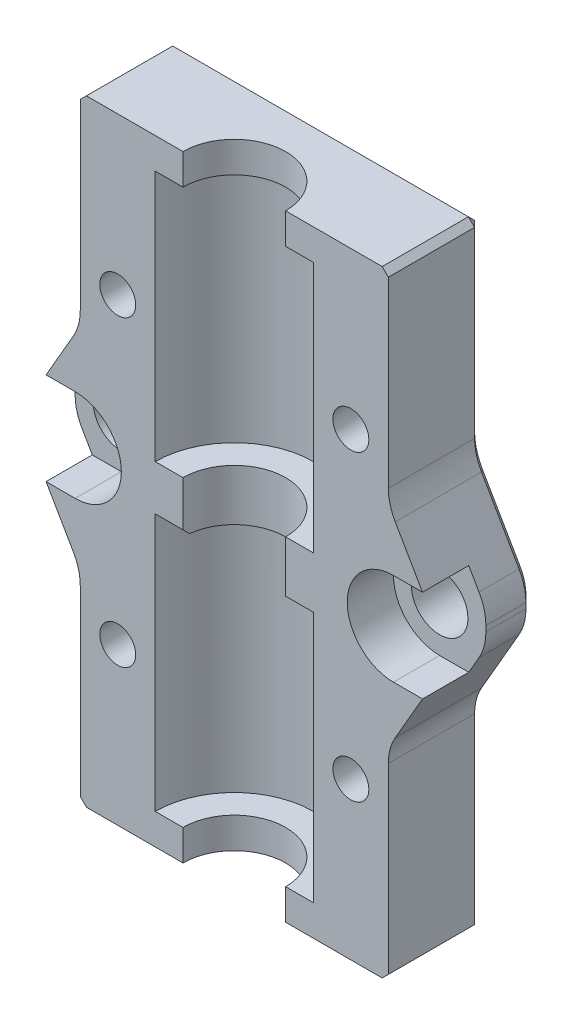
SolidWorks part; units mm, degrees
material "ABS"
ref_plane "Plano frontal" through (0, 0, 0) normal (0, 0, 1) x (1, 0, 0)
ref_plane "Plano superior" through (0, 0, 0) normal (0, 1, 0) x (1, 0, 0)
ref_plane "Plano direito" through (0, 0, 0) normal (1, 0, 0) x (0, 0, -1)
sketch "Esboço1" plane through (0, 0, 0) normal (0, 0, 1) x (1, 0, 0)
  line L1 (-15, 30) -> (15, 30)
  line L2 (-15, 30) -> (-15, -30)
  line L3 (-15, -30) -> (15, -30)
  line L4 (15, 30) -> (15, -30)
  line L5 (-15, 30) -> (15, -30) construction
  line L6 (-15, -30) -> (15, 30) construction
  point P0 (0, 0)
  dimension "D1" = 30
  dimension "D2" = 60
extrude "Ressalto-extrusão1" add sketch "Esboço1" along normal mid plane 9
sketch "Esboço2" plane through (0, -30, 0) normal (0, -1, 0) x (1, 0, 0)
  line L0 (-15, 4.5) -> (15, 4.5) construction
  arc A0 (-5, 4.5) -> (5, 4.5) centre (0, 4.5) ccw
  dimension "D1" = 5
extrude "Corte-extrusão2" cut sketch "Esboço2" against normal through all
ref_plane "Plano1" through (0, 27, 0) normal (0, 1, 0) x (1, 0, 0)
sketch "Esboço3" plane through (0, 27, 0) normal (0, 1, 0) x (1, 0, 0)
  line L5 (5, -4.5) -> (15, -4.5)
  line L6 (15, -4.5) -> (15, 4.5)
  line L7 (15, 4.5) -> (-15, 4.5)
  line L8 (-15, 4.5) -> (-15, -4.5)
  line L9 (-15, -4.5) -> (-5, -4.5)
  line L10 (5, -4.5) -> (15, -4.5)
  line L11 (15, -4.5) -> (15, 4.5)
  line L12 (15, 4.5) -> (-15, 4.5)
  line L13 (-15, 4.5) -> (-15, -4.5)
  line L14 (-15, -4.5) -> (-5, -4.5)
  arc A0 (7.7, -4.5) -> (-7.7, -4.5) centre (0, -4.5) ccw
  arc A1 (5, -4.5) -> (-5, -4.5) centre (0, -4.5) ccw
  arc A2 (5, -4.5) -> (-5, -4.5) centre (0, -4.5) ccw
  dimension "D2" = 7.7
  dimension "D1" = 0
extrude "Corte-extrusão3" cut sketch "Esboço3" against normal blind 24.5 contours A2 L10 A0 L14 region at (0, 27, -0.6722)
mirror "Espelhar1" about plane through (0, 0, 0) normal (0, 1, 0) of "Corte-extrusão3"
sketch "Esboço4" plane through (15, 0, 0) normal (1, 0, 0) x (0, 0, -1)
  line L0 (4.5, -30) -> (4.5, 30) construction
  line L1 (-4.5, -12) -> (4.5, -12)
  line L2 (-4.5, -12) -> (-4.5, 12)
  line L3 (-4.5, 12) -> (4.5, 12)
  line L4 (4.5, -12) -> (4.5, 12)
  line L5 (-4.5, -12) -> (4.5, 12) construction
  line L6 (-4.5, 12) -> (4.5, -12) construction
  point P0 (0, 0)
  dimension "D1" = 24
extrude "Ressalto-extrusão3" add sketch "Esboço4" along normal blind 5
chamfer "Chanfro1" distance 6 angle 60 2 edges at (20, 12, 0) (20, -12, 0) first distance on face at (17.5, 12, 0) first distance on face at (17.5, -12, 0)
fillet "Filete2" radius 5 4 edges at (20, 1.6077, 0) (20, -1.6077, 0) (15, 10.2679, 0) (15, -10.2679, 0)
mirror "Espelhar2" about plane through (0, 0, 0) normal (1, 0, 0) of "Ressalto-extrusão3", "Chanfro1"
fillet "Filete3" radius 5 4 edges at (-15, -10.2679, 0) (-15, 10.2679, 0) (-20, 1.6077, 0) (-20, -1.6077, 0)
sketch "Esboço5" plane through (0, 0, 4.5) normal (0, 0, 1) x (1, 0, 0)
  line L0 (20, 0.2679) -> (20, -0.2679) construction
  line L1 (-20, 0) -> (20, 0) construction
  line L2 (-20, 0.2679) -> (-20, -0.2679) construction
  circle A0 centre (15.5, 0) radius 2.75
  point P5 (20, 0)
  dimension "D1" = 4.5
  dimension "D2" = 5.5
extrude "Corte-extrusão4" cut sketch "Esboço5" against normal through all
sketch "Esboço6" plane through (0, 0, 4.5) normal (0, 0, 1) x (1, 0, 0)
  line L0 (15.5, 4.5) -> (18.3301, 4.5)
  line L1 (19.3301, 2.7679) -> (15.6699, 9.1077) construction
  line L2 (20, 0.2679) -> (20, -0.2679) construction
  line L3 (15.5, -4.5) -> (18.3301, -4.5)
  line L4 (15.6699, -9.1077) -> (19.3301, -2.7679) construction
  circle A0 centre (15.5, 0) radius 4.5
  point P9 (20, 0)
  circle M3 centre (15.5, 0) radius 2.75
  line M4 (20, -0.2679) -> (20, 0.2679)
  arc M5 (20, 0.2679) -> (19.3301, 2.7679) centre (15, 0.2679) ccw
  line M6 (19.3301, 2.7679) -> (15.6699, 9.1077)
  line M22 (15.6699, -9.1077) -> (19.3301, -2.7679)
  arc M23 (19.3301, -2.7679) -> (20, -0.2679) centre (15, -0.2679) ccw
extrude "Corte-extrusão5" cut sketch "Esboço6" against normal blind 4.5 contours A0 L0 M4 M5 M6 | A0 M3 | A0 L3 M22 M23 M4 region at (18.3101, 3.6055, 4.5) region at (18.592, 3.092, 4.5) region at (18.3101, -3.6055, 4.5)
mirror "Espelhar5" about plane through (0, 0, 0) normal (1, 0, 0) of "Corte-extrusão5", "Corte-extrusão4"
sketch "Esboço7" plane through (0, 0, 4.5) normal (0, 0, 1) x (1, 0, 0)
  line L0 (7.7, 14.75) -> (15, 14.75) construction
  line L1 (7.7, 2.5) -> (7.7, 27) construction
  line L2 (15, 11.6077) -> (15, 30) construction
  circle A0 centre (11.35, 14.75) radius 1.75
  dimension "D1" = 3.5
extrude "Corte-extrusão6" cut sketch "Esboço7" against normal through all
mirror "Espelhar3" about plane through (0, 0, 0) normal (0, 1, 0) of "Corte-extrusão6"
mirror "Espelhar4" about plane through (0, 0, 0) normal (1, 0, 0) of "Espelhar3"
chamfer "Chanfro2" distance 0.6 angle 45 25 edges at (-6.35, -2.5, 4.5) (-20, 0, -4.5) (-19.8296, -1.562, -4.5) (-17.5, -5.9378, -4.5) (-15.1704, -10.3136, -4.5) (-15, -20.8038, -4.5) (0, -30, -4.5) (15, -20.8038, -4.5) (15.1704, -10.3136, -4.5) (17.5, -5.9378, -4.5) (19.8296, -1.562, -4.5) (20, 0, -4.5) (19.8296, 1.562, -4.5) (17.5, 5.9378, -4.5) (15.1704, 10.3136, -4.5) (-19.8296, 1.562, -4.5) (-17.5, 5.9378, -4.5) (-15.1704, 10.3136, -4.5) (15, 20.8038, -4.5) (0, 30, -4.5) (-15, 20.8038, -4.5) (-15, -30, 0) (-15, 30, 0) (15, -30, 0) (15, 30, 0)
